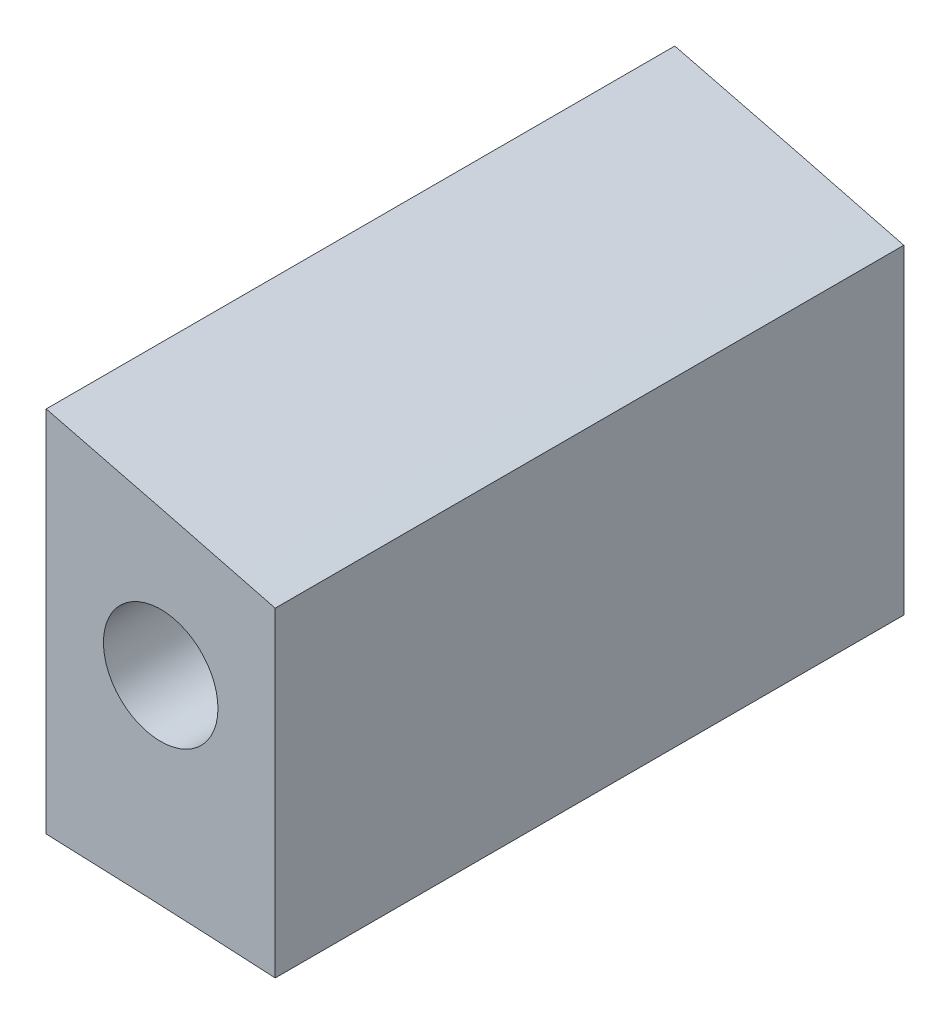
SolidWorks part; units mm, degrees
ref_plane "Front Plane" through (0, 0, 0) normal (0, 0, 1) x (1, 0, 0)
ref_plane "Top Plane" through (0, 0, 0) normal (0, 1, 0) x (1, 0, 0)
ref_plane "Right Plane" through (0, 0, 0) normal (1, 0, 0) x (0, 0, -1)
sketch "Sketch1" plane through (0, 0, 0) normal (0, 0, 1) x (1, 0, 0)
  spline S0 degree 3 poles (0.0006, 0.0001) (0.8106, 7.3592) (8.6491, 17.8566) (26.2867, 29.9752) (52.1111, 42.0692) (89.5976, 49.2908) (131.4008, 47.8848) (173.2567, 40.0411) (217.9611, 29.613) (256.9521, 19.5289) (290.3598, 8.711) (301.2732, 4.3828) (314.8169, -0.5162) (309.8463, 0.0001) knots 0 0 0 0 0.060864 0.113688 0.188609 0.312909 0.448482 0.557612 0.691544 0.852438 0.929756 0.976058 1 1 1 1
  spline S1 degree 3 poles (309.8463, 0.0001) (303.9568, 1.471) (293.9895, 2.094) (276.264, 4.5144) (260.8463, 5.4274) (235.8588, 7.8703) (205.1014, 8.8381) (157.7186, 9.0307) (110.4973, 6.1815) (66.5062, -0.5867) (36.4547, -6.0985) (15.3166, -6.1891) (1.2307, -6.9241) (0.0006, 0.0001) knots 0 0 0 0 0.057787 0.095275 0.171021 0.205339 0.335319 0.464904 0.658702 0.785512 0.893517 0.943092 1 1 1 1
extrude "Boss-Extrude1" add sketch "Sketch1" along normal blind 34.8615
sketch "Sketch2" plane through (0, 0, 34.8615) normal (0, 0, 1) x (1, 0, 0)
  line L1 (372.5284, -56.283) -> (233.6463, -56.283)
  line L2 (372.5284, -56.283) -> (372.5284, 95.9913)
  line L3 (372.5284, 95.9913) -> (233.6463, 95.9913)
  line L4 (233.6463, -56.283) -> (233.6463, 95.9913)
  circle A0 centre (20.32, 10.16) radius 6.35
  circle A1 centre (227.2963, 19.0501) radius 3.175
  dimension "D2" = 12.7
  dimension "D3" = 6.35
  dimension "D6" = 20.32
  dimension "D1" = 82.55
  dimension "D4" = 19.05
  dimension "D5" = 10.16
  dimension "D7" = 6.35
extrude "Cut-Extrude1" cut sketch "Sketch2" against normal through all
sketch "Sketch3" plane through (0, 0, 34.8615) normal (0, 0, 1) x (1, 0, 0)
  line L0 (233.6463, 25.4528) -> (233.6463, 7.6905) construction
  line L1 (-72.2426, 88.4657) -> (220.9463, 88.4657)
  line L2 (-72.2426, 88.4657) -> (-72.2426, -49.5056)
  line L3 (-72.2426, -49.5056) -> (220.9463, -49.5056)
  line L4 (220.9463, 88.4657) -> (220.9463, -49.5056)
  dimension "D1" = 12.7
extrude "Cut-Extrude2" cut sketch "Sketch3" against normal through all
